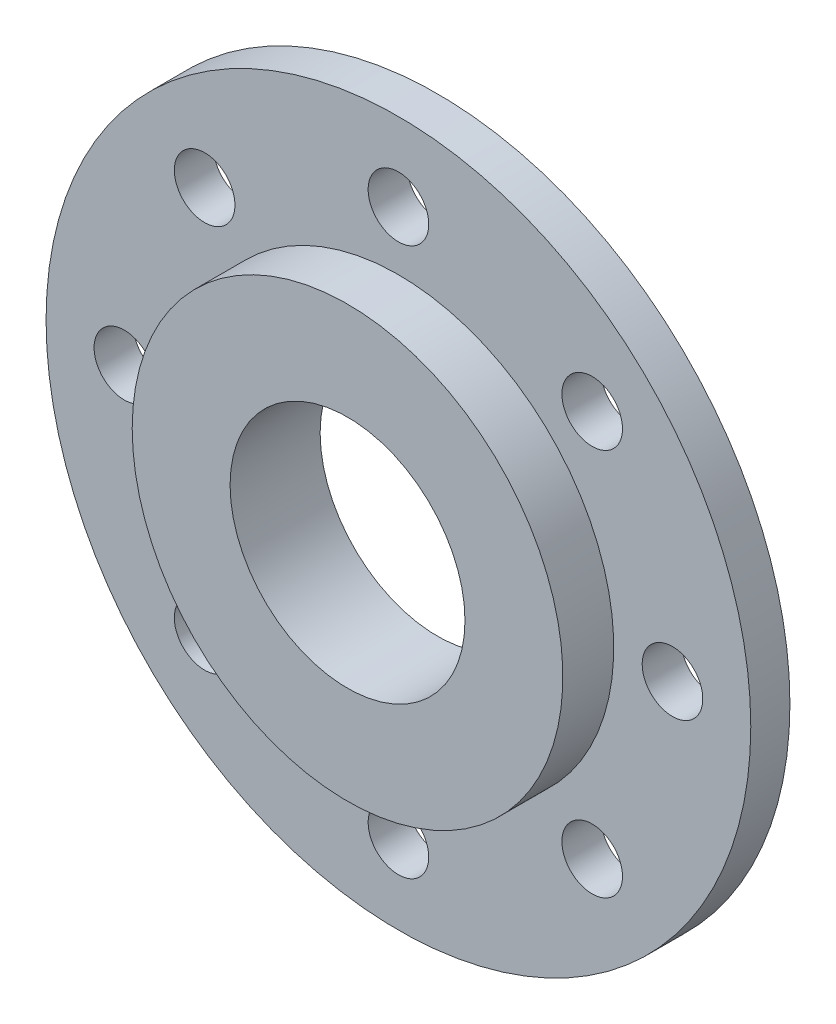
SolidWorks part; units mm, degrees
ref_plane "Front Plane" through (0, 0, 0) normal (0, 0, 1) x (1, 0, 0)
ref_plane "Top Plane" through (0, 0, 0) normal (0, 1, 0) x (1, 0, 0)
ref_plane "Right Plane" through (0, 0, 0) normal (1, 0, 0) x (0, 0, -1)
sketch "Sketch1" plane through (0, 0, 0) normal (0, 0, 1) x (1, 0, 0)
  circle A0 centre (0, 0) radius 17.4625
  dimension "D1" = 34.925
extrude "Boss-Extrude1" add sketch "Sketch1" along normal blind 4.1275
sketch "Sketch2" plane through (0, 0, 0) normal (0, 0, -1) x (-1, 0, 0)
  circle A0 centre (0, 0) radius 28.575
  dimension "D1" = 57.15
extrude "Boss-Extrude2" add sketch "Sketch2" along normal blind 3.175
hole_wizard "#10 (0.1935) Diameter Hole1" positions "Sketch3" profile "Sketch4" hole size "#10" standard "ANSI Inch" end condition through all
sketch "Sketch3" plane through (0, 0, -3.175) normal (0, 0, -1) x (-1, 0, 0)
  point P0 (0, 22.225)
  dimension "D1" = 22.225
sketch "Sketch4" plane through (0, 22.225, -3.175) normal (1, 0, 0) x (0, 1, 0)
  line L0 (0, 0) -> (0, 7.3025)
  line L1 (0, 7.3025) -> (2.4574, 7.3025)
  line L2 (2.4574, 7.3025) -> (2.4574, 0)
  line L5 (2.4574, 0) -> (0, 0)
  line L11 (0, -6.35) -> (0, 107.95) construction
  dimension "Thru Hole Dia." = 4.9149
  dimension "Thru Hole Depth" = 7.3025
pattern_circular "CirPattern1" count 8 over 360 about axis through (0, 0, -3.175) along (0, 0, -1) of "#10 (0.1935) Diameter Hole1"
sketch "Sketch5" plane through (0, 0, -3.175) normal (0, 0, -1) x (-1, 0, 0)
  circle A0 centre (0, 0) radius 9.525
  dimension "D1" = 19.05
extrude "Cut-Extrude1" cut sketch "Sketch5" against normal up to next
